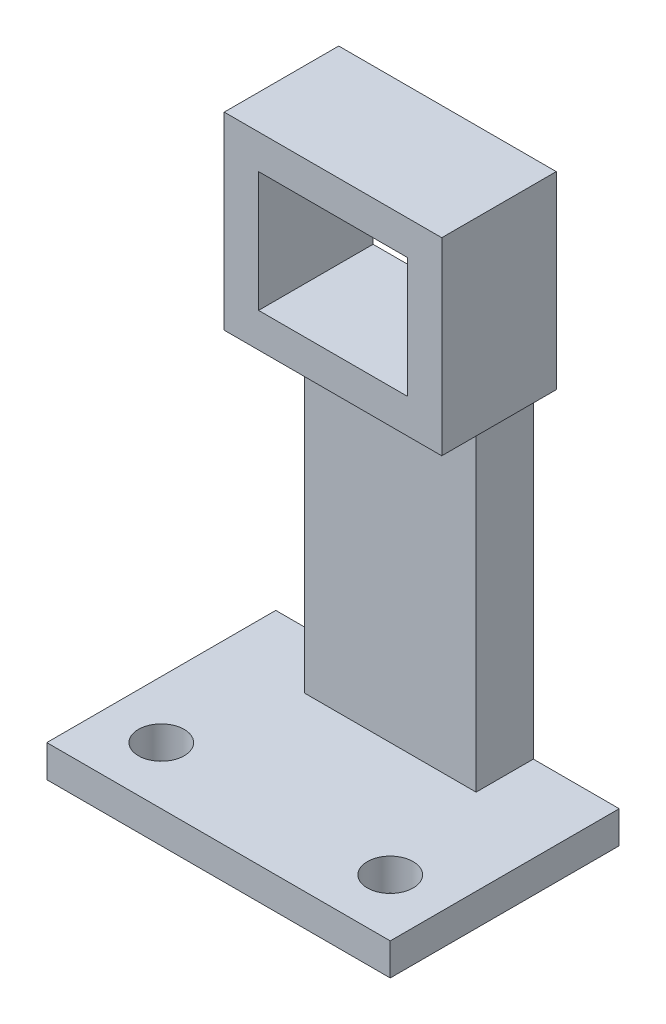
SolidWorks part; units mm, degrees
ref_plane "Front Plane" through (0, 0, 0) normal (0, 0, 1) x (1, 0, 0)
ref_plane "Top Plane" through (0, 0, 0) normal (0, 1, 0) x (1, 0, 0)
ref_plane "Right Plane" through (0, 0, 0) normal (1, 0, 0) x (0, 0, -1)
sketch "Sketch1" plane through (0, 0, 0) normal (0, 0, 1) x (1, 0, 0)
  line L0 (0, 0) -> (0, -40)
  line L1 (6.5, 5.25) -> (-6.5, 5.25)
  line L2 (6.5, 5.25) -> (6.5, -5.25)
  line L3 (6.5, -5.25) -> (-6.5, -5.25)
  line L4 (-6.5, 5.25) -> (-6.5, -5.25)
  line L5 (6.5, 5.25) -> (-6.5, -5.25) construction
  line L6 (6.5, -5.25) -> (-6.5, 5.25) construction
  line L8 (9.5, 8.25) -> (-9.5, 8.25)
  line L9 (9.5, 8.25) -> (9.5, -8.25)
  line L10 (9.5, -8.25) -> (-9.5, -8.25)
  line L11 (-9.5, 8.25) -> (-9.5, -8.25)
  line L12 (9.5, 8.25) -> (-9.5, -8.25) construction
  line L13 (9.5, -8.25) -> (-9.5, 8.25) construction
  line L14 (7.5, 0) -> (-7.5, 0)
  line L15 (7.5, 0) -> (7.5, -40)
  line L16 (7.5, -40) -> (-7.5, -40)
  line L17 (-7.5, 0) -> (-7.5, -40)
  line L18 (7.5, 0) -> (-7.5, -40) construction
  line L19 (7.5, -40) -> (-7.5, 0) construction
  line L20 (-15, -40) -> (15, -40)
  line L21 (-15, -40) -> (-15, -37.192)
  line L22 (-15, -37.192) -> (15, -37.192)
  line L23 (15, -40) -> (15, -37.192)
  point P0 (0, 0)
  point P12 (0, -20)
  dimension "D1" = 13
  dimension "D2" = 10.5
  dimension "D3" = 40
  dimension "D4" = 3
  dimension "D5" = 3
  dimension "D6" = 15
  dimension "D7" = 15
  dimension "D8" = 30
extrude "Boss-Extrude1" add sketch "Sketch1" along normal blind 10 contours L17 L14 L4 L1 L2 L15 L10 L9 L8 L11 | L14 L17 L10 L0 L3 L4 | L15 L14 L2 L3 L0 L10 region at (4.3649, -5.9696, 0) region at (-4.3649, -5.9696, 0) region at (6.7516, 2.625, 0)
extrude "Boss-Extrude2" add sketch "Sketch1<3>" along normal blind 5 contours L17 L22 L0 L10 | L0 L22 L15 L10 region at (3.75, -22.721, 0) region at (-3.75, -22.721, 0)
sketch "Sketch1<3>" plane through (0, 0, 0) normal (0, 0, 1) x (1, 0, 0) same geometry as "Sketch1"
extrude "Boss-Extrude3" add sketch "Sketch1<4>" along normal blind 20 contours L22 L23 L20 L21
sketch "Sketch1<4>" plane through (0, 0, 0) normal (0, 0, 1) x (1, 0, 0) same geometry as "Sketch1"
sketch "Sketch2" plane through (0, -37.192, 0) normal (0, 1, 0) x (1, 0, 0)
  line L0 (-15, -20) -> (-15, 0) construction
  line L1 (-15, -20) -> (15, -20) construction
  circle A0 centre (-10, -15) radius 2
  circle A1 centre (10, -15) radius 2
  dimension "D1" = 4
  dimension "D2" = 4
  dimension "D3" = 20
  dimension "D4" = 5
  dimension "D5" = 5
extrude "Cut-Extrude1" cut sketch "Sketch2" against normal blind 20
